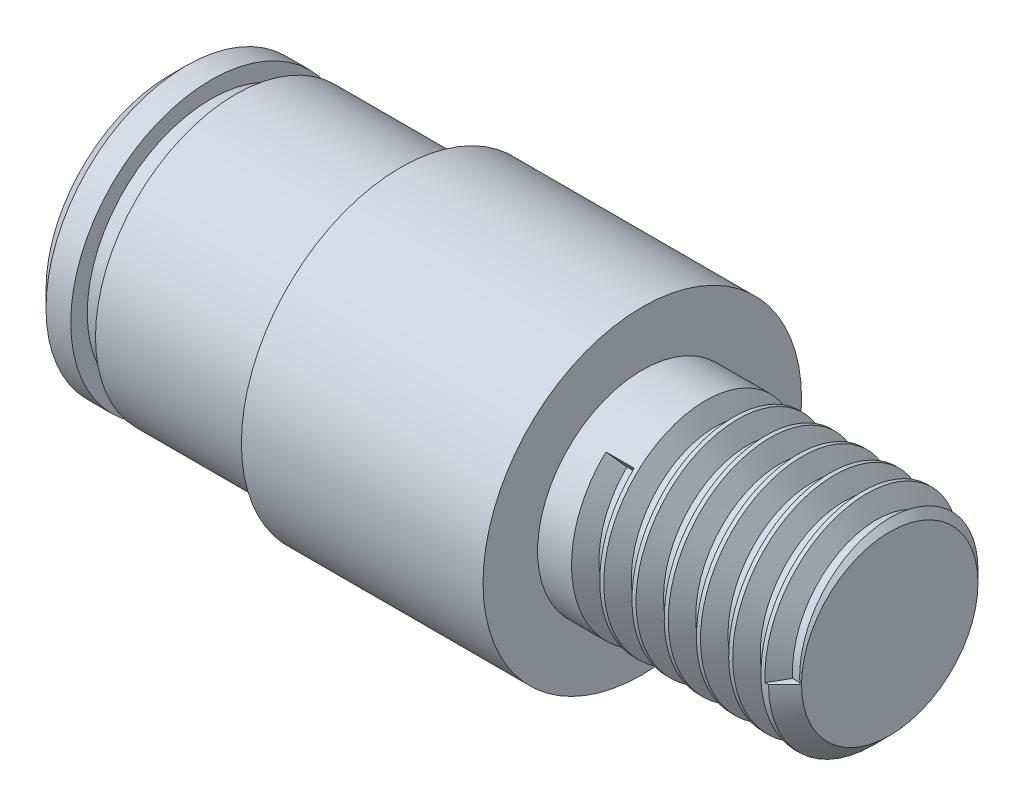
SolidWorks part; units mm, degrees
material "AISI 1020"
ref_plane "Alzado" through (0, 0, 0) normal (0, 0, 1) x (1, 0, 0)
ref_plane "Planta" through (0, 0, 0) normal (0, 1, 0) x (1, 0, 0)
ref_plane "Vista lateral" through (0, 0, 0) normal (1, 0, 0) x (0, 0, -1)
sketch "Croquis1" plane through (0, 0, 0) normal (0, 0, 1) x (1, 0, 0)
  line L0 (0, 0) -> (-57.6, 0) construction
  line L1 (-43.65, 0) -> (-43.65, 8.5)
  line L2 (-43.65, 8.5) -> (-29.65, 8.5)
  line L3 (-29.65, 8.5) -> (-29.65, 9.655)
  line L4 (-29.65, 9.655) -> (-15, 9.655)
  line L5 (-15, 9.655) -> (-15, 6.35)
  line L6 (-15, 6.35) -> (0, 6.35)
  line L7 (0, 6.35) -> (0, 0)
  line L8 (0, 0) -> (-43.65, 0)
  dimension "D1" = 14.65
  dimension "D2" = 15
  dimension "D3" = 12.7
  dimension "D4" = 17
  dimension "D5" = 14
revolve "Revolución1" add sketch "Croquis1" angle 360 about L0
chamfer "Chaflán1" distance 1 angle 45 1 edges at (0, 0, -6.35)
thread "Rosca1" pitch 1.9538 method cut profile "Perfil de rosca1" start angle 0, offset 1.5, length 12, pitch 1.9538, diameter 12.7
ref_plane "Plano1" through (0.5, 0, 6.35) normal (0, -1, 0) x (0, 0, 1)
sketch "Perfil de rosca1" plane through (0.5, 0, 6.35) normal (0, -1, 0) x (0, 0, 1)
  line L0 (0, 0) -> (0, 1.9538) construction
  line L11 (0, 0) -> (0, 1.7096)
  line L12 (0, 1.7096) -> (-1.0576, 1.099)
  line L13 (-1.0576, 1.099) -> (-1.0576, 0.6106)
  line L15 (-1.0576, 0.6106) -> (0, 0)
  line L17 (-1.0576, 0.8548) -> (0, 0.8548) construction
  point P2 (0, 0)
  dimension "Pitch" = 1.9538
  dimension "Profile_Angle" = 60
  dimension "Profile_Land" = 0.4885
  dimension "Profile_Height" = 1.0576
chamfer "Chaflán2" distance 1 angle 45 1 edges at (-43.65, 0, -8.5)
sketch "Croquis5" plane through (0, 0, 0) normal (0, 0, 1) x (1, 0, 0)
  line L0 (-29.65, 8.5) -> (-42.65, 8.5) construction
  line L1 (-41.15, 9.5) -> (-39.65, 9.5)
  line L2 (-41.15, 9.5) -> (-41.15, 7.5)
  line L3 (-41.15, 7.5) -> (-39.65, 7.5)
  line L4 (-39.65, 9.5) -> (-39.65, 7.5)
  line L5 (-41.15, 9.5) -> (-39.65, 7.5) construction
  line L6 (-41.15, 7.5) -> (-39.65, 9.5) construction
  line L7 (-29.65, 9.655) -> (-29.65, -9.655) construction
  line L8 (0, 0) -> (-51.4925, 0) construction
  point P0 (-40.4, 8.5)
  dimension "D1" = 1.5
  dimension "D2" = 2
  dimension "D3" = 10
revolve "Cortar-Revolución1" cut sketch "Croquis5" angle 360 about L8
